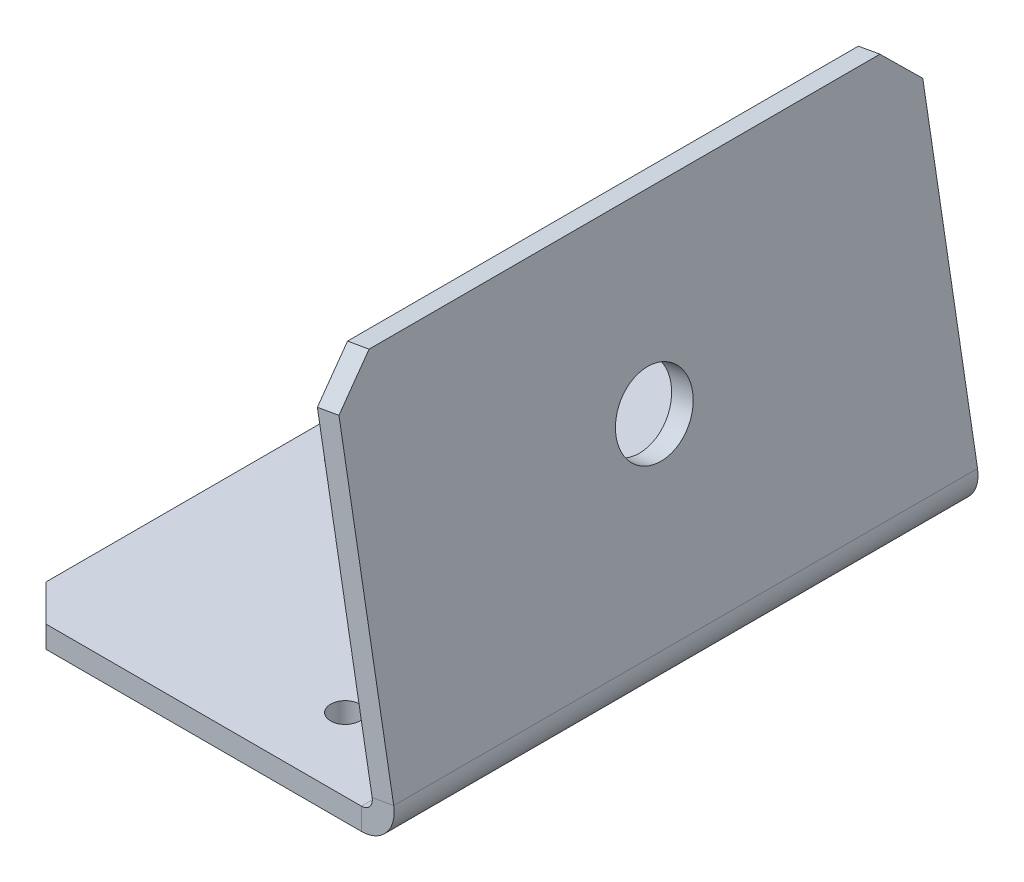
SolidWorks part; units mm, degrees
note: The reader was unsure of these and kept them because the rebuilt part matched: flange length of "Edge-Flange1".
ref_plane "Front Plane" through (0, 0, 0) normal (0, 0, 1) x (1, 0, 0)
ref_plane "Top Plane" through (0, 0, 0) normal (0, 1, 0) x (1, 0, 0)
ref_plane "Right Plane" through (0, 0, 0) normal (1, 0, 0) x (0, 0, -1)
sketch "Sketch1" plane through (0, 0, 0) normal (0, 1, 0) x (1, 0, 0)
  line L1 (-25, 40) -> (25, 40)
  line L2 (-25, 40) -> (-25, -40)
  line L3 (-25, -40) -> (25, -40)
  line L4 (25, 40) -> (25, -40)
  line L5 (-25, 40) -> (25, -40) construction
  line L6 (-25, -40) -> (25, 40) construction
  point P0 (0, 0)
  dimension "D1" = 50
  dimension "D2" = 80
sheet metal parameters "Sheet-Metal1" thickness 3 parameters "D1"=1.5
base flange "Base-Flange1" sketch "Sketch1" thickness 3 reverse thickness direction no parameters "D1"=1.5
edge flange "Edge-Flange1" sketch "Sketch6" flange angle 80 flange length 50 flange position material outside bend radius 1.5 thickness 3 relief rectangular parameters "D6"=10
sketch "Sketch6" plane through (25, 0, 0) normal (0.9848, 0.1736, 0) x (0, 0, -1)
  line L0 (-40, 0) -> (40, 0) construction
  line L1 (-40, 0) -> (40, 0)
  line L2 (-40, 0) -> (-40, 50)
  line L3 (-40, 50) -> (40, 50)
  line L4 (40, 50) -> (40, 0)
bend "EdgeBend1" bend radius 1.5 bend angle 100 parameters "D5"=1
chamfer "Chamfer1" distance 5 angle 45 4 edges at (-25, -1.5, -40) (17.7948, 49.5009, -40) (-25, -1.5, 40) (17.7948, 49.5009, 40)
sketch "Sketch7" plane through (27.2006, 4.7962, 0) normal (0.9848, 0.1736, 0) x (0, 0, -1)
  line L0 (0, 47.9307) -> (0, -9.9405) construction
  line L1 (35, 45.6588) -> (-35, 45.6588) construction
  circle A0 centre (0, 22.1588) radius 5.25
  dimension "D1" = 10.5
  dimension "D2" = 23.5
extrude "Cut-Extrude1" cut sketch "Sketch7" against normal blind 10 normal cut yes
sketch "Sketch8" plane through (0, -3, 0) normal (0, -1, 0) x (1, 0, 0)
  line L0 (-35.5272, 0) -> (43.2528, 0) construction
  line L1 (-25, -35) -> (-25, 35) construction
  circle A0 centre (-19, 0) radius 2
  circle A1 centre (11, 30) radius 2
  circle A2 centre (11, -30) radius 2
  dimension "D1" = 4
  dimension "D3" = 4
  dimension "D4" = 30
  dimension "D5" = 30
  dimension "D2" = 6
extrude "Cut-Extrude2" cut sketch "Sketch8" against normal up to next normal cut yes
flat pattern "Flat-Pattern1" [suppressed]
sketch "Bend-Lines1" plane through (0, 0, 0) normal (0, 1, 0) x (1, 0, 0)
sketch3d "Bounding-Box1" [suppressed]
  line L0 (25, 40, 0) -> (25, -40, 0) construction
  line L1 (-25, 40, 0) -> (-25, -40, 0) construction
  line L2 (25, 40, 0) -> (-25, 40, 0) construction
  line L3 (25, -40, 0) -> (-25, -40, 0) construction
bend of the flat pattern "Flatten-<EdgeBend1>1"
